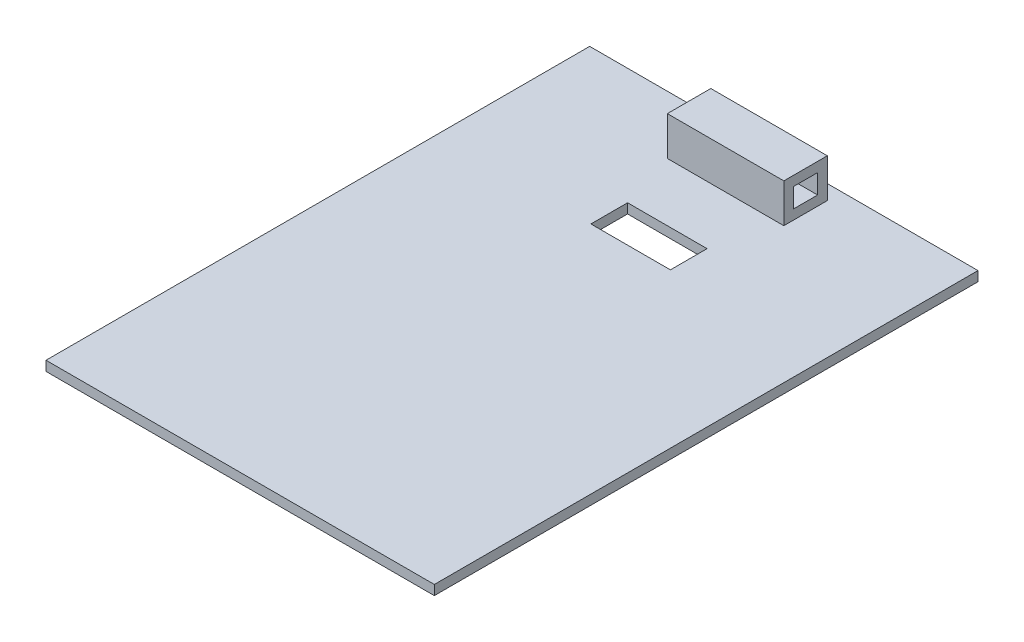
SolidWorks part; units mm, degrees
ref_plane "Front Plane" through (0, 0, 0) normal (0, 0, 1) x (1, 0, 0)
ref_plane "Top Plane" through (0, 0, 0) normal (0, 1, 0) x (1, 0, 0)
ref_plane "Right Plane" through (0, 0, 0) normal (1, 0, 0) x (0, 0, -1)
sketch "Sketch1" plane through (0, 0, 0) normal (0, 1, 0) x (1, 0, 0)
  line L0 (63.5, 177.8) -> (63.5, 0) construction
  line L1 (0, 0) -> (127, 0)
  line L2 (0, 0) -> (0, 177.8)
  line L3 (0, 177.8) -> (127, 177.8)
  line L4 (127, 0) -> (127, 177.8)
  line L5 (50.5, 139.7) -> (76.5, 139.7)
  line L6 (50.5, 139.7) -> (50.5, 127.7)
  line L7 (50.5, 127.7) -> (76.5, 127.7)
  line L8 (76.5, 139.7) -> (76.5, 127.7)
  line L9 (63.5, 139.7) -> (63.5, 127.7) construction
  point P9 (50.5, 160.6991)
  dimension "D1" = 127
  dimension "D2" = 177.8
  dimension "D3" = 26
  dimension "D4" = 12
  dimension "D5" = 38.1
extrude "Boss-Extrude2" add sketch "Sketch1" along normal blind 3.175
ref_plane "Plane1" through (0, 0, -158.75) normal (0, 0, -1) x (-1, 0, 0)
sketch "Sketch5" plane through (0, 0, -158.75) normal (0, 0, -1) x (-1, 0, 0)
  line L0 (-127, 3.175) -> (0, 3.175) construction
  line L1 (-82.55, 15.875) -> (-44.45, 15.875)
  line L2 (-82.55, 15.875) -> (-82.55, 3.175)
  line L3 (-82.55, 3.175) -> (-44.45, 3.175)
  line L4 (-44.45, 15.875) -> (-44.45, 3.175)
  line L5 (-63.5, 15.875) -> (-63.5, 3.175) construction
  line L6 (-63.5, 3.175) -> (-63.5, 0) construction
  line L7 (-127, 0) -> (0, 0) construction
  dimension "D1" = 12.7
  dimension "D2" = 38.1
extrude "Boss-Extrude3" add sketch "Sketch5" along normal blind 14.224
sketch "Sketch8" plane through (82.55, 0, 0) normal (1, 0, 0) x (0, 0, -1)
  line L0 (172.974, 15.875) -> (172.974, 3.175) construction
  line L1 (161.925, 12.7) -> (169.799, 12.7)
  line L2 (161.925, 12.7) -> (161.925, 6.35)
  line L3 (161.925, 6.35) -> (169.799, 6.35)
  line L4 (169.799, 12.7) -> (169.799, 6.35)
  line L5 (172.974, 15.875) -> (158.75, 15.875) construction
  line L9 (158.75, -22.942) -> (158.75, 22.942) construction
  line L10 (172.974, 3.175) -> (158.75, 3.175) construction
  dimension "D1" = 3.175
  dimension "D2" = 3.175
  dimension "D3" = 3.175
  dimension "D4" = 3.175
extrude "Cut-Extrude1" cut sketch "Sketch8" against normal up to next
